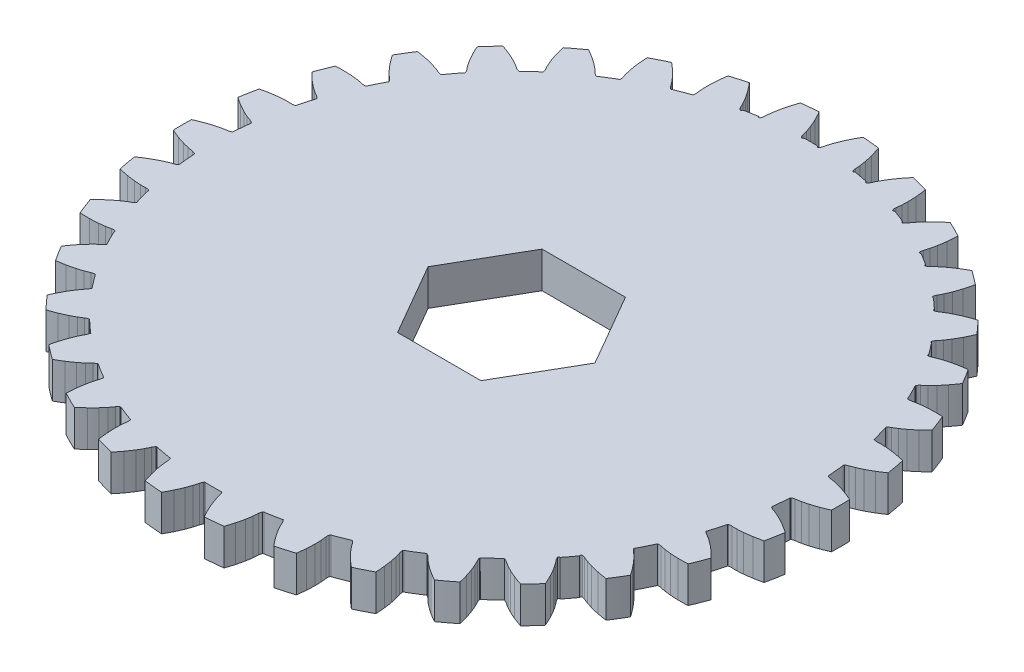
SolidWorks part; units mm, degrees
ref_plane "Front Plane" through (0, 0, 0) normal (0, 0, 1) x (1, 0, 0)
ref_plane "Top Plane" through (0, 0, 0) normal (0, 1, 0) x (1, 0, 0)
ref_plane "Right Plane" through (0, 0, 0) normal (1, 0, 0) x (0, 0, -1)
sketch "Model" plane through (0, 0, 0) normal (0, 1, 0) x (1, 0, 0)
  line L1 (7.3323, 0) -> (3.6662, 6.35)
  line L2 (3.6662, 6.35) -> (-3.6662, 6.35)
  line L3 (-3.6662, 6.35) -> (-7.3323, 0)
  line L4 (-7.3323, 0) -> (-3.6662, -6.35)
  line L5 (-3.6662, -6.35) -> (3.6662, -6.35)
  line L6 (3.6662, -6.35) -> (7.3323, 0)
  circle A0 centre (0, 0) radius 27.7 construction
  arc A1 (26.1185, -2.4202) -> (26.1766, -1.6798) centre (0, 0) ccw
  arc A2 (26.2183, -1.6388) -> (26.1766, -1.6798) centre (26.263, -1.726) ccw
  arc A3 (26.4889, -1.5535) -> (26.2183, -1.6388) centre (26.6041, -2.3907) ccw
  arc A4 (26.4889, -1.5535) -> (26.9416, -1.473) centre (25.6873, 4.2688) ccw
  arc A5 (26.9416, -1.473) -> (27.4742, -1.3382) centre (25.1508, 6.7249) ccw
  arc A6 (27.4742, -1.3382) -> (28.1662, -1.11) centre (24.8202, 7.8723) ccw
  arc A7 (28.1662, -1.11) -> (28.9229, -0.7986) centre (23.9466, 10.2174) ccw
  arc A8 (28.9229, -0.7986) -> (28.9229, 0.7986) centre (0, 0) ccw
  arc A9 (28.9229, 0.7986) -> (28.1662, 1.11) centre (23.9466, -10.2174) ccw
  arc A10 (28.1662, 1.11) -> (27.4742, 1.3382) centre (24.8202, -7.8723) ccw
  arc A11 (27.4742, 1.3382) -> (26.9416, 1.473) centre (25.1508, -6.7249) ccw
  arc A12 (26.9416, 1.473) -> (26.4889, 1.5535) centre (25.6873, -4.2688) ccw
  arc A13 (26.2183, 1.6388) -> (26.4889, 1.5535) centre (26.6041, 2.3907) ccw
  arc A14 (26.1675, 1.6852) -> (26.2183, 1.6388) centre (26.2566, 1.7318) ccw
  arc A15 (26.1675, 1.6852) -> (26.0357, 3.1176) centre (0, 0) ccw
  arc A16 (26.073, 3.2067) -> (26.0357, 3.1176) centre (26.133, 3.1292) ccw
  arc A17 (26.3233, 3.3403) -> (26.073, 3.2067) centre (26.5904, 2.5385) ccw
  arc A18 (26.3233, 3.3403) -> (26.7535, 3.5026) centre (24.4655, 8.9161) ccw
  arc A19 (26.7535, 3.5026) -> (27.2523, 3.7329) centre (23.4869, 11.2318) ccw
  arc A20 (27.2523, 3.7329) -> (27.8906, 4.0844) centre (22.951, 12.2989) ccw
  arc A21 (27.8906, 4.0844) -> (28.5771, 4.5296) centre (21.6614, 14.4436) ccw
  arc A22 (28.5771, 4.5296) -> (28.2837, 6.0995) centre (0, 0) ccw
  arc A23 (28.2837, 6.0995) -> (27.4827, 6.2666) centre (25.4163, -5.6432) ccw
  arc A24 (27.4827, 6.2666) -> (26.7605, 6.3638) centre (25.8441, -3.1775) ccw
  arc A25 (26.7605, 6.3638) -> (26.2122, 6.3984) centre (25.9582, -1.9889) ccw
  arc A26 (26.2122, 6.3984) -> (25.7524, 6.3943) centre (26.0343, 0.5239) ccw
  arc A27 (25.4707, 6.4285) -> (25.7524, 6.3943) centre (25.7119, 7.2385) ccw
  arc A28 (25.4168, 6.447) -> (25.4707, 6.4285) centre (25.4771, 6.5347) ccw
  arc A29 (25.4168, 6.447) -> (25.0195, 7.8485) centre (0, 0) ccw
  arc A30 (25.0398, 7.943) -> (25.0195, 7.8485) centre (25.113, 7.8779) ccw
  arc A31 (25.2613, 8.1203) -> (25.0398, 7.943) centre (25.6712, 7.3813) ccw
  arc A32 (25.2613, 8.1203) -> (25.6544, 8.3589) centre (22.4106, 13.2599) ccw
  arc A33 (25.6544, 8.3589) -> (26.1024, 8.677) centre (21.0231, 15.3563) ccw
  arc A34 (26.1024, 8.677) -> (26.6652, 9.1398) centre (20.3003, 16.3068) ccw
  arc A35 (26.6652, 9.1398) -> (27.2583, 9.7035) centre (18.6386, 18.1779) ccw
  arc A36 (27.2583, 9.7035) -> (26.6813, 11.1928) centre (0, 0) ccw
  arc A37 (26.6813, 11.1928) -> (25.8632, 11.2099) centre (26.0205, -0.8769) ccw
  arc A38 (25.8632, 11.2099) -> (25.1355, 11.1727) centre (25.9879, 1.6254) ccw
  arc A39 (25.1355, 11.1727) -> (24.5902, 11.1059) centre (25.8817, 2.8148) ccw
  arc A40 (24.5902, 11.1059) -> (24.139, 11.0175) centre (25.4948, 5.2988) ccw
  arc A41 (23.8558, 10.9993) -> (24.139, 11.0175) centre (23.944, 11.8398) ccw
  arc A42 (23.8034, 10.9988) -> (23.8558, 10.9993) centre (23.8287, 11.1089) ccw
  arc A43 (23.8034, 10.9988) -> (23.1514, 12.3122) centre (0, 0) ccw
  arc A44 (23.154, 12.4088) -> (23.1514, 12.3122) centre (23.2379, 12.3582) ccw
  arc A45 (23.3391, 12.6238) -> (23.154, 12.4088) centre (23.8778, 11.9727) ccw
  arc A46 (23.3391, 12.6238) -> (23.6816, 12.9306) centre (19.5926, 17.152) ccw
  arc A47 (23.6816, 12.9306) -> (24.0635, 13.3255) centre (17.8434, 18.9578) ccw
  arc A48 (24.0635, 13.3255) -> (24.5317, 13.8838) centre (16.9583, 19.7593) ccw
  arc A49 (24.5317, 13.8838) -> (25.0418, 14.5927) centre (14.981, 21.2932) ccw
  arc A50 (25.0418, 14.5927) -> (24.225, 15.9119) centre (0, 0) ccw
  arc A51 (24.225, 15.9119) -> (23.363, 15.7713) centre (25.7385, 3.9192) ccw
  arc A52 (23.363, 15.7713) -> (22.6546, 15.6011) centre (25.2467, 6.373) ccw
  arc A53 (22.6546, 15.6011) -> (22.1308, 15.4353) centre (24.9238, 7.5226) ccw
  arc A54 (22.1308, 15.4353) -> (21.7035, 15.2654) centre (24.087, 9.8932) ccw
  arc A55 (21.4285, 15.1955) -> (21.7035, 15.2654) centre (21.3607, 16.0379) ccw
  arc A56 (21.4336, 15.196) -> (21.4285, 15.1955) centre (21.4207, 15.2932) ccw
  arc A57 (21.4336, 15.196) -> (20.5895, 16.3215) centre (0, 0) ccw
  arc A58 (20.4796, 16.4521) -> (20.5895, 16.3215) centre (20.5714, 16.4178) ccw
  arc A59 (20.6221, 16.6974) -> (20.4796, 16.4521) centre (21.2713, 16.1563) ccw
  arc A60 (20.6221, 16.6974) -> (20.9024, 17.0619) centre (16.1073, 20.4601) ccw
  arc A61 (20.9024, 17.0619) -> (21.2052, 17.5203) centre (14.0561, 21.9137) ccw
  arc A62 (21.2052, 17.5203) -> (21.5629, 18.1551) centre (13.0388, 22.5389) ccw
  arc A63 (21.5629, 18.1551) -> (21.9401, 18.96) centre (10.8133, 23.6834) ccw
  arc A64 (21.9401, 18.96) -> (20.9035, 20.0971) centre (0, 0) ccw
  arc A65 (20.9035, 20.0971) -> (20.0673, 19.7958) centre (24.5801, 8.582) ccw
  arc A66 (20.0673, 19.7958) -> (19.4021, 19.4982) centre (23.6458, 10.9036) ccw
  arc A67 (19.4021, 19.4982) -> (18.9177, 19.239) centre (23.1172, 11.9742) ccw
  arc A68 (18.9177, 19.239) -> (18.5289, 18.9935) centre (21.859, 14.1507) ccw
  arc A69 (18.2715, 18.8742) -> (18.5289, 18.9935) centre (18.0501, 19.6899) ccw
  arc A70 (18.2887, 18.8807) -> (18.2715, 18.8742) centre (18.2458, 18.9688) ccw
  arc A71 (18.2887, 18.8807) -> (17.2519, 19.8325) centre (0, 0) ccw
  arc A72 (17.1078, 19.935) -> (17.2519, 19.8325) centre (17.2044, 19.9182) ccw
  arc A73 (17.2028, 20.2024) -> (17.1078, 19.935) centre (17.9404, 19.7898) ccw
  arc A74 (17.2028, 20.2024) -> (17.4114, 20.6122) centre (12.0735, 23.0714) ccw
  arc A75 (17.4114, 20.6122) -> (17.6248, 21.1184) centre (9.7902, 24.1234) ccw
  arc A76 (17.6248, 21.1184) -> (17.8597, 21.8082) centre (8.6753, 24.551) ccw
  arc A77 (17.8597, 21.8082) -> (18.0855, 22.6818) centre (6.2774, 25.2671) ccw
  arc A78 (18.0855, 22.6818) -> (16.8666, 23.6023) centre (0, 0) ccw
  arc A79 (16.8666, 23.6023) -> (16.0881, 23.146) centre (22.5847, 12.9524) ccw
  arc A80 (16.0881, 23.146) -> (15.489, 22.7314) centre (21.2397, 15.0628) ccw
  arc A81 (15.489, 22.7314) -> (15.0605, 22.3875) centre (20.5233, 16.0181) ccw
  arc A82 (15.0605, 22.3875) -> (14.7234, 22.0748) centre (18.8866, 17.9264) ccw
  arc A83 (14.4923, 21.9102) -> (14.7234, 22.0748) centre (14.1247, 22.6713) ccw
  arc A84 (14.5162, 21.9266) -> (14.4923, 21.9102) centre (14.4496, 21.9985) ccw
  arc A85 (14.5162, 21.9266) -> (13.3218, 22.6721) centre (0, 0) ccw
  arc A86 (13.1535, 22.7392) -> (13.3218, 22.6721) centre (13.2515, 22.7404) ccw
  arc A87 (13.1977, 23.0194) -> (13.1535, 22.7392) centre (13.9986, 22.7494) ccw
  arc A88 (13.1977, 23.0194) -> (13.3275, 23.4605) centre (7.6285, 24.8971) ccw
  arc A89 (13.3275, 23.4605) -> (13.4442, 23.9974) centre (5.1908, 25.5116) ccw
  arc A90 (13.4442, 23.9974) -> (13.5484, 24.7186) centre (4.0163, 25.7271) ccw
  arc A91 (13.5484, 24.7186) -> (13.6101, 25.6297) centre (1.5277, 25.9904) ccw
  arc A92 (13.6101, 25.6297) -> (12.251, 26.3064) centre (0, 0) ccw
  arc A93 (12.251, 26.3064) -> (11.5611, 25.7081) centre (19.8201, 16.8818) ccw
  arc A94 (11.5611, 25.7081) -> (11.0484, 25.1904) centre (18.1103, 18.7091) ccw
  arc A95 (11.0484, 25.1904) -> (10.6903, 24.7737) centre (17.2305, 19.5165) ccw
  arc A96 (10.6903, 24.7737) -> (10.4165, 24.4043) centre (15.2711, 21.0916) ccw
  arc A97 (10.2195, 24.2001) -> (10.4165, 24.4043) centre (9.7184, 24.8807) ccw
  arc A98 (10.2447, 24.2274) -> (10.2195, 24.2001) centre (10.1614, 24.279) ccw
  arc A99 (10.2447, 24.2274) -> (8.9332, 24.741) centre (0, 0) ccw
  arc A100 (8.7512, 24.7689) -> (8.9332, 24.741) centre (8.8473, 24.7881) ccw
  arc A101 (8.7432, 25.0526) -> (8.7512, 24.7689) centre (9.58, 24.9343) ccw
  arc A102 (8.7432, 25.0526) -> (8.7897, 25.51) centre (2.9238, 25.8749) ccw
  arc A103 (8.7897, 25.51) -> (8.8058, 26.0592) centre (0.4147, 26.031) ccw
  arc A104 (8.8058, 26.0592) -> (8.7757, 26.7872) centre (-0.7794, 26.027) ccw
  arc A105 (8.7757, 26.7872) -> (8.6677, 27.702) centre (-3.2741, 25.8285) ccw
  arc A106 (8.6677, 27.702) -> (7.2138, 28.1157) centre (0, 0) ccw
  arc A107 (7.2138, 28.1157) -> (6.6404, 27.3947) centre (16.3806, 20.2363) ccw
  arc A108 (6.6404, 27.3947) -> (6.2315, 26.7916) centre (14.3641, 21.7183) ccw
  arc A109 (6.2315, 26.7916) -> (5.9562, 26.3162) centre (13.351, 22.3503) ccw
  arc A110 (5.9562, 26.3162) -> (5.7549, 25.9028) centre (11.1355, 23.5385) ccw
  arc A111 (5.5987, 25.6659) -> (5.7549, 25.9028) centre (4.9811, 26.2428) ccw
  arc A112 (5.6203, 25.7026) -> (5.5987, 25.6659) centre (5.5271, 25.7328) ccw
  arc A113 (5.6203, 25.7026) -> (4.2365, 25.9665) centre (0, 0) ccw
  arc A114 (4.0509, 25.9552) -> (4.2365, 25.9665) centre (4.1419, 25.9917) ccw
  arc A115 (3.9909, 26.2325) -> (4.0509, 25.9552) centre (4.8352, 26.2701) ccw
  arc A116 (3.9909, 26.2325) -> (3.9526, 26.6907) centre (-1.8805, 25.9716) ccw
  arc A117 (3.9526, 26.6907) -> (3.8675, 27.2335) centre (-4.3756, 25.664) ccw
  arc A118 (3.8675, 27.2335) -> (3.7041, 27.9436) centre (-5.5486, 25.4406) ccw
  arc A119 (3.7041, 27.9436) -> (3.4283, 28.8275) centre (-7.9643, 24.7872) ccw
  arc A120 (3.4283, 28.8275) -> (1.9271, 28.9666) centre (0, 0) ccw
  arc A121 (1.9271, 28.9666) -> (1.4936, 28.1485) centre (12.3833, 22.9017) ccw
  arc A122 (1.4936, 28.1485) -> (1.2025, 27.4805) centre (10.1288, 23.9879) ccw
  arc A123 (1.2025, 27.4805) -> (1.0191, 26.9626) centre (9.0168, 24.423) ccw
  arc A124 (1.0191, 26.9626) -> (0.8972, 26.5192) centre (6.6207, 25.1839) ccw
  arc A125 (0.7873, 26.2576) -> (0.8972, 26.5192) centre (0.0742, 26.7112) ccw
  arc A126 (0.8021, 26.3003) -> (0.7873, 26.2576) centre (0.7046, 26.3102) ccw
  arc A127 (0.8021, 26.3003) -> (-0.6068, 26.3056) centre (0, 0) ccw
  arc A128 (-0.7873, 26.2576) -> (-0.6068, 26.3056) centre (-0.7046, 26.3102) ccw
  arc A129 (-0.8972, 26.5192) -> (-0.7873, 26.2576) centre (-0.0742, 26.7112) ccw
  arc A130 (-0.8972, 26.5192) -> (-1.0191, 26.9626) centre (-6.6207, 25.1839) ccw
  arc A131 (-1.0191, 26.9626) -> (-1.2025, 27.4805) centre (-9.0168, 24.423) ccw
  arc A132 (-1.2025, 27.4805) -> (-1.4936, 28.1485) centre (-10.1288, 23.9879) ccw
  arc A133 (-1.4936, 28.1485) -> (-1.9277, 28.9676) centre (-12.3833, 22.9017) ccw
  arc A134 (-1.9277, 28.9676) -> (-3.4279, 28.8286) centre (0, 0) ccw
  arc A135 (-3.4279, 28.8286) -> (-3.7041, 27.9436) centre (7.9643, 24.7872) ccw
  arc A136 (-3.7041, 27.9436) -> (-3.8675, 27.2335) centre (5.5486, 25.4406) ccw
  arc A137 (-3.8675, 27.2335) -> (-3.9526, 26.6907) centre (4.3756, 25.664) ccw
  arc A138 (-3.9526, 26.6907) -> (-3.9909, 26.2325) centre (1.8805, 25.9716) ccw
  arc A139 (-4.0509, 25.9552) -> (-3.9909, 26.2325) centre (-4.8352, 26.2701) ccw
  arc A140 (-4.0442, 25.9995) -> (-4.0509, 25.9552) centre (-4.1419, 25.9917) ccw
  arc A141 (-4.0442, 25.9995) -> (-5.43, 25.7458) centre (0, 0) ccw
  arc A142 (-5.5987, 25.6659) -> (-5.43, 25.7458) centre (-5.5271, 25.7328) ccw
  arc A143 (-5.7549, 25.9028) -> (-5.5987, 25.6659) centre (-4.9811, 26.2428) ccw
  arc A144 (-5.7549, 25.9028) -> (-5.9562, 26.3162) centre (-11.1355, 23.5385) ccw
  arc A145 (-5.9562, 26.3162) -> (-6.2315, 26.7916) centre (-13.351, 22.3503) ccw
  arc A146 (-6.2315, 26.7916) -> (-6.6404, 27.3947) centre (-14.3641, 21.7183) ccw
  arc A147 (-6.6404, 27.3947) -> (-7.2161, 28.1184) centre (-16.3806, 20.2363) ccw
  arc A148 (-7.2161, 28.1184) -> (-8.6671, 27.7055) centre (0, 0) ccw
  arc A149 (-8.6671, 27.7055) -> (-8.7757, 26.7872) centre (3.2741, 25.8285) ccw
  arc A150 (-8.7757, 26.7872) -> (-8.8058, 26.0592) centre (0.7794, 26.027) ccw
  arc A151 (-8.8058, 26.0592) -> (-8.7897, 25.51) centre (-0.4147, 26.031) ccw
  arc A152 (-8.7897, 25.51) -> (-8.7432, 25.0526) centre (-2.9238, 25.8749) ccw
  arc A153 (-8.7512, 24.7689) -> (-8.7432, 25.0526) centre (-9.58, 24.9343) ccw
  arc A154 (-8.7401, 24.7222) -> (-8.7512, 24.7689) centre (-8.8779, 24.7141) ccw
  arc A155 (-8.7401, 24.7222) -> (-10.1236, 24.1886) centre (0, 0) ccw
  arc A156 (-10.2195, 24.2001) -> (-10.1236, 24.1886) centre (-10.1614, 24.279) ccw
  arc A157 (-10.4165, 24.4043) -> (-10.2195, 24.2001) centre (-9.7184, 24.8807) ccw
  arc A158 (-10.4165, 24.4043) -> (-10.6903, 24.7737) centre (-15.2711, 21.0916) ccw
  arc A159 (-10.6903, 24.7737) -> (-11.0484, 25.1904) centre (-17.2305, 19.5165) ccw
  arc A160 (-11.0484, 25.1904) -> (-11.5611, 25.7081) centre (-18.1103, 18.7091) ccw
  arc A161 (-11.5611, 25.7081) -> (-12.1772, 26.2467) centre (-19.8201, 16.8818) ccw
  arc A162 (-12.1772, 26.2467) -> (-13.6069, 25.5347) centre (0, 0) ccw
  arc A163 (-13.6069, 25.5347) -> (-13.5484, 24.7186) centre (-1.5277, 25.9904) ccw
  arc A164 (-13.5484, 24.7186) -> (-13.4442, 23.9974) centre (-4.0163, 25.7271) ccw
  arc A165 (-13.4442, 23.9974) -> (-13.3275, 23.4605) centre (-5.1908, 25.5116) ccw
  arc A166 (-13.3275, 23.4605) -> (-13.1977, 23.0194) centre (-7.6285, 24.8971) ccw
  arc A167 (-13.1535, 22.7392) -> (-13.1977, 23.0194) centre (-13.9986, 22.7494) ccw
  arc A168 (-13.1353, 22.6945) -> (-13.1535, 22.7392) centre (-13.2668, 22.6671) ccw
  arc A169 (-13.1353, 22.6945) -> (-14.3959, 21.9166) centre (0, 0) ccw
  arc A170 (-14.4923, 21.9102) -> (-14.3959, 21.9166) centre (-14.4496, 21.9985) ccw
  arc A171 (-14.7234, 22.0748) -> (-14.4923, 21.9102) centre (-14.1247, 22.6713) ccw
  arc A172 (-14.7234, 22.0748) -> (-15.0605, 22.3875) centre (-18.8866, 17.9264) ccw
  arc A173 (-15.0605, 22.3875) -> (-15.489, 22.7314) centre (-20.5233, 16.0181) ccw
  arc A174 (-15.489, 22.7314) -> (-16.0881, 23.146) centre (-21.2397, 15.0628) ccw
  arc A175 (-16.0881, 23.146) -> (-16.7926, 23.5622) centre (-22.5847, 12.9524) ccw
  arc A176 (-16.7926, 23.5622) -> (-18.0672, 22.5997) centre (0, 0) ccw
  arc A177 (-18.0672, 22.5997) -> (-17.8597, 21.8082) centre (-6.2774, 25.2671) ccw
  arc A178 (-17.8597, 21.8082) -> (-17.6248, 21.1184) centre (-8.6753, 24.551) ccw
  arc A179 (-17.6248, 21.1184) -> (-17.4114, 20.6122) centre (-9.7902, 24.1234) ccw
  arc A180 (-17.4114, 20.6122) -> (-17.2028, 20.2024) centre (-12.0735, 23.0714) ccw
  arc A181 (-17.1078, 19.935) -> (-17.2028, 20.2024) centre (-17.9404, 19.7898) ccw
  arc A182 (-17.0837, 19.8928) -> (-17.1078, 19.935) centre (-17.2059, 19.851) ccw
  arc A183 (-17.0837, 19.8928) -> (-18.1779, 18.8982) centre (0, 0) ccw
  arc A184 (-18.2715, 18.8742) -> (-18.1779, 18.8982) centre (-18.2458, 18.9688) ccw
  arc A185 (-18.5289, 18.9935) -> (-18.2715, 18.8742) centre (-18.0501, 19.6899) ccw
  arc A186 (-18.5289, 18.9935) -> (-18.9177, 19.239) centre (-21.859, 14.1507) ccw
  arc A187 (-18.9177, 19.239) -> (-19.4021, 19.4982) centre (-23.1172, 11.9742) ccw
  arc A188 (-19.4021, 19.4982) -> (-20.0673, 19.7958) centre (-23.6458, 10.9036) ccw
  arc A189 (-20.0673, 19.7958) -> (-20.8363, 20.0754) centre (-24.5801, 8.582) ccw
  arc A190 (-20.8363, 20.0754) -> (-21.9123, 18.8951) centre (0, 0) ccw
  arc A191 (-21.9123, 18.8951) -> (-21.5629, 18.1551) centre (-10.8133, 23.6834) ccw
  arc A192 (-21.5629, 18.1551) -> (-21.2052, 17.5203) centre (-13.0388, 22.5389) ccw
  arc A193 (-21.2052, 17.5203) -> (-20.9024, 17.0619) centre (-14.0561, 21.9137) ccw
  arc A194 (-20.9024, 17.0619) -> (-20.6221, 16.6974) centre (-16.1073, 20.4601) ccw
  arc A195 (-20.4796, 16.4521) -> (-20.6221, 16.6974) centre (-21.2713, 16.1563) ccw
  arc A196 (-20.4506, 16.4119) -> (-20.4796, 16.4521) centre (-20.5624, 16.3616) ccw
  arc A197 (-20.4506, 16.4119) -> (-21.3409, 15.2362) centre (0, 0) ccw
  arc A198 (-21.4285, 15.1955) -> (-21.3409, 15.2362) centre (-21.4207, 15.2932) ccw
  arc A199 (-21.7035, 15.2654) -> (-21.4285, 15.1955) centre (-21.3607, 16.0379) ccw
  arc A200 (-21.7035, 15.2654) -> (-22.1308, 15.4353) centre (-24.087, 9.8932) ccw
  arc A201 (-22.1308, 15.4353) -> (-22.6546, 15.6011) centre (-24.9238, 7.5226) ccw
  arc A202 (-22.6546, 15.6011) -> (-23.363, 15.7713) centre (-25.2467, 6.373) ccw
  arc A203 (-23.363, 15.7713) -> (-24.1703, 15.9049) centre (-25.7385, 3.9192) ccw
  arc A204 (-24.1703, 15.9049) -> (-25.0111, 14.547) centre (0, 0) ccw
  arc A205 (-25.0111, 14.547) -> (-24.5317, 13.8838) centre (-14.981, 21.2932) ccw
  arc A206 (-24.5317, 13.8838) -> (-24.0635, 13.3255) centre (-16.9583, 19.7593) ccw
  arc A207 (-24.0635, 13.3255) -> (-23.6816, 12.9306) centre (-17.8434, 18.9578) ccw
  arc A208 (-23.6816, 12.9306) -> (-23.3391, 12.6238) centre (-19.5926, 17.152) ccw
  arc A209 (-23.154, 12.4088) -> (-23.3391, 12.6238) centre (-23.8778, 11.9727) ccw
  arc A210 (-23.1209, 12.3694) -> (-23.154, 12.4088) centre (-23.2234, 12.3168) ccw
  arc A211 (-23.1209, 12.3694) -> (-23.7772, 11.0554) centre (0, 0) ccw
  arc A212 (-23.8558, 10.9993) -> (-23.7772, 11.0554) centre (-23.866, 11.0967) ccw
  arc A213 (-24.139, 11.0175) -> (-23.8558, 10.9993) centre (-23.944, 11.8398) ccw
  arc A214 (-24.139, 11.0175) -> (-24.5902, 11.1059) centre (-25.4948, 5.2988) ccw
  arc A215 (-24.5902, 11.1059) -> (-25.1355, 11.1727) centre (-25.8817, 2.8148) ccw
  arc A216 (-25.1355, 11.1727) -> (-25.8632, 11.2099) centre (-25.9879, 1.6254) ccw
  arc A217 (-25.8632, 11.2099) -> (-26.6813, 11.1928) centre (-26.0205, -0.8769) ccw
  arc A218 (-26.6813, 11.1928) -> (-27.2583, 9.7035) centre (0, 0) ccw
  arc A219 (-27.2583, 9.7035) -> (-26.6652, 9.1398) centre (-18.6386, 18.1779) ccw
  arc A220 (-26.6652, 9.1398) -> (-26.1024, 8.677) centre (-20.3003, 16.3068) ccw
  arc A221 (-26.1024, 8.677) -> (-25.6544, 8.3589) centre (-21.0231, 15.3563) ccw
  arc A222 (-25.6544, 8.3589) -> (-25.2613, 8.1203) centre (-22.4106, 13.2599) ccw
  arc A223 (-25.0398, 7.943) -> (-25.2613, 8.1203) centre (-25.6712, 7.3813) ccw
  arc A224 (-25.0029, 7.9012) -> (-25.0398, 7.943) centre (-25.0995, 7.8532) ccw
  arc A225 (-25.0029, 7.9012) -> (-25.4038, 6.4981) centre (0, 0) ccw
  arc A226 (-25.4707, 6.4285) -> (-25.4038, 6.4981) centre (-25.4987, 6.5224) ccw
  arc A227 (-25.7524, 6.3943) -> (-25.4707, 6.4285) centre (-25.7119, 7.2385) ccw
  arc A228 (-25.7524, 6.3943) -> (-26.2122, 6.3984) centre (-26.0343, 0.5239) ccw
  arc A229 (-26.2122, 6.3984) -> (-26.7605, 6.3638) centre (-25.9582, -1.9889) ccw
  arc A230 (-26.7605, 6.3638) -> (-27.4827, 6.2666) centre (-25.8441, -3.1775) ccw
  arc A231 (-27.4827, 6.2666) -> (-28.2837, 6.0995) centre (-25.4163, -5.6432) ccw
  arc A232 (-28.2837, 6.0995) -> (-28.5771, 4.5296) centre (0, 0) ccw
  arc A233 (-28.5771, 4.5296) -> (-27.8906, 4.0844) centre (-21.6614, 14.4436) ccw
  arc A234 (-27.8906, 4.0844) -> (-27.2523, 3.7329) centre (-22.951, 12.2989) ccw
  arc A235 (-27.2523, 3.7329) -> (-26.7535, 3.5026) centre (-23.4869, 11.2318) ccw
  arc A236 (-26.7535, 3.5026) -> (-26.3233, 3.3403) centre (-24.4655, 8.9161) ccw
  arc A237 (-26.073, 3.2067) -> (-26.3233, 3.3403) centre (-26.5904, 2.5385) ccw
  arc A238 (-26.0313, 3.1538) -> (-26.073, 3.2067) centre (-26.1269, 3.1214) ccw
  arc A239 (-26.0313, 3.1538) -> (-26.1652, 1.7195) centre (0, 0) ccw
  arc A240 (-26.2183, 1.6388) -> (-26.1652, 1.7195) centre (-26.263, 1.726) ccw
  arc A241 (-26.4889, 1.5535) -> (-26.2183, 1.6388) centre (-26.6041, 2.3907) ccw
  arc A242 (-26.4889, 1.5535) -> (-26.9416, 1.473) centre (-25.6873, -4.2688) ccw
  arc A243 (-26.9416, 1.473) -> (-27.4742, 1.3382) centre (-25.1508, -6.7249) ccw
  arc A244 (-27.4742, 1.3382) -> (-28.1662, 1.11) centre (-24.8202, -7.8723) ccw
  arc A245 (-28.1662, 1.11) -> (-28.9229, 0.7986) centre (-23.9466, -10.2174) ccw
  arc A246 (-28.9229, 0.7986) -> (-28.9229, -0.7986) centre (0, 0) ccw
  arc A247 (-28.9229, -0.7986) -> (-28.1662, -1.11) centre (-23.9466, 10.2174) ccw
  arc A248 (-28.1662, -1.11) -> (-27.4742, -1.3382) centre (-24.8202, 7.8723) ccw
  arc A249 (-27.4742, -1.3382) -> (-26.9416, -1.473) centre (-25.1508, 6.7249) ccw
  arc A250 (-26.9416, -1.473) -> (-26.4889, -1.5535) centre (-25.6873, 4.2688) ccw
  arc A251 (-26.2183, -1.6388) -> (-26.4889, -1.5535) centre (-26.6041, -2.3907) ccw
  arc A252 (-26.1719, -1.762) -> (-26.2183, -1.6388) centre (-26.263, -1.726) ccw
  arc A253 (-26.1719, -1.762) -> (-26.0401, -3.1604) centre (0, 0) ccw
  arc A254 (-26.073, -3.2067) -> (-26.0401, -3.1604) centre (-26.133, -3.1292) ccw
  arc A255 (-26.3233, -3.3403) -> (-26.073, -3.2067) centre (-26.5904, -2.5385) ccw
  arc A256 (-26.3233, -3.3403) -> (-26.7535, -3.5026) centre (-24.4655, -8.9161) ccw
  arc A257 (-26.7535, -3.5026) -> (-27.2523, -3.7329) centre (-23.4869, -11.2318) ccw
  arc A258 (-27.2523, -3.7329) -> (-27.8906, -4.0844) centre (-22.951, -12.2989) ccw
  arc A259 (-27.8906, -4.0844) -> (-28.595, -4.5421) centre (-21.6614, -14.4436) ccw
  arc A260 (-28.595, -4.5421) -> (-28.3049, -6.0944) centre (0, 0) ccw
  arc A261 (-28.3049, -6.0944) -> (-27.4827, -6.2666) centre (-25.4163, 5.6432) ccw
  arc A262 (-27.4827, -6.2666) -> (-26.7605, -6.3638) centre (-25.8441, 3.1775) ccw
  arc A263 (-26.7605, -6.3638) -> (-26.2122, -6.3984) centre (-25.9582, 1.9889) ccw
  arc A264 (-26.2122, -6.3984) -> (-25.7524, -6.3943) centre (-26.0343, -0.5239) ccw
  arc A265 (-25.4707, -6.4285) -> (-25.7524, -6.3943) centre (-25.7119, -7.2385) ccw
  arc A266 (-25.4134, -6.5706) -> (-25.4707, -6.4285) centre (-25.4987, -6.5224) ccw
  arc A267 (-25.4134, -6.5706) -> (-25.0253, -7.9214) centre (0, 0) ccw
  arc A268 (-25.0398, -7.943) -> (-25.0253, -7.9214) centre (-25.113, -7.8779) ccw
  arc A269 (-25.2613, -8.1203) -> (-25.0398, -7.943) centre (-25.6712, -7.3813) ccw
  arc A270 (-25.2613, -8.1203) -> (-25.6544, -8.3589) centre (-22.4106, -13.2599) ccw
  arc A271 (-25.6544, -8.3589) -> (-26.1024, -8.677) centre (-21.0231, -15.3563) ccw
  arc A272 (-26.1024, -8.677) -> (-26.6652, -9.1398) centre (-20.3003, -16.3068) ccw
  arc A273 (-26.6652, -9.1398) -> (-27.288, -9.7339) centre (-18.6386, -18.1779) ccw
  arc A274 (-27.288, -9.7339) -> (-26.7237, -11.1904) centre (0, 0) ccw
  arc A275 (-26.7237, -11.1904) -> (-25.8632, -11.2099) centre (-26.0205, 0.8769) ccw
  arc A276 (-25.8632, -11.2099) -> (-25.1355, -11.1727) centre (-25.9879, -1.6254) ccw
  arc A277 (-25.1355, -11.1727) -> (-24.5902, -11.1059) centre (-25.8817, -2.8148) ccw
  arc A278 (-24.5902, -11.1059) -> (-24.139, -11.0175) centre (-25.4948, -5.2988) ccw
  arc A279 (-23.8558, -10.9993) -> (-24.139, -11.0175) centre (-23.944, -11.8398) ccw
  arc A280 (-23.7824, -11.1478) -> (-23.8558, -10.9993) centre (-23.866, -11.0967) ccw
  arc A281 (-23.7824, -11.1478) -> (-23.1517, -12.4048) centre (0, 0) ccw
  arc A282 (-23.154, -12.4088) -> (-23.1517, -12.4048) centre (-23.2379, -12.3582) ccw
  arc A283 (-23.3391, -12.6238) -> (-23.154, -12.4088) centre (-23.8778, -11.9727) ccw
  arc A284 (-23.3391, -12.6238) -> (-23.6816, -12.9306) centre (-19.5926, -17.152) ccw
  arc A285 (-23.6816, -12.9306) -> (-24.0635, -13.3255) centre (-17.8434, -18.9578) ccw
  arc A286 (-24.0635, -13.3255) -> (-24.5317, -13.8838) centre (-16.9583, -19.7593) ccw
  arc A287 (-24.5317, -13.8838) -> (-25.0111, -14.547) centre (-14.981, -21.2932) ccw
  arc A288 (-25.0111, -14.547) -> (-24.1703, -15.9049) centre (0, 0) ccw
  arc A289 (-24.1703, -15.9049) -> (-23.363, -15.7713) centre (-25.7385, -3.9192) ccw
  arc A290 (-23.363, -15.7713) -> (-22.6546, -15.6011) centre (-25.2467, -6.373) ccw
  arc A291 (-22.6546, -15.6011) -> (-22.1308, -15.4353) centre (-24.9238, -7.5226) ccw
  arc A292 (-22.1308, -15.4353) -> (-21.7035, -15.2654) centre (-24.087, -9.8932) ccw
  arc A293 (-21.4285, -15.1955) -> (-21.7035, -15.2654) centre (-21.3607, -16.0379) ccw
  arc A294 (-21.3409, -15.2362) -> (-21.4285, -15.1955) centre (-21.4207, -15.2932) ccw
  arc A295 (-21.3409, -15.2362) -> (-20.4506, -16.4119) centre (0, 0) ccw
  arc A296 (-20.4796, -16.4521) -> (-20.4506, -16.4119) centre (-20.5624, -16.3616) ccw
  arc A297 (-20.6221, -16.6974) -> (-20.4796, -16.4521) centre (-21.2713, -16.1563) ccw
  arc A298 (-20.6221, -16.6974) -> (-20.9024, -17.0619) centre (-16.1073, -20.4601) ccw
  arc A299 (-20.9024, -17.0619) -> (-21.2052, -17.5203) centre (-14.0561, -21.9137) ccw
  arc A300 (-21.2052, -17.5203) -> (-21.5629, -18.1551) centre (-13.0388, -22.5389) ccw
  arc A301 (-21.5629, -18.1551) -> (-21.9123, -18.8951) centre (-10.8133, -23.6834) ccw
  arc A302 (-21.9123, -18.8951) -> (-20.8363, -20.0754) centre (0, 0) ccw
  arc A303 (-20.8363, -20.0754) -> (-20.0673, -19.7958) centre (-24.5801, -8.582) ccw
  arc A304 (-20.0673, -19.7958) -> (-19.4021, -19.4982) centre (-23.6458, -10.9036) ccw
  arc A305 (-19.4021, -19.4982) -> (-18.9177, -19.239) centre (-23.1172, -11.9742) ccw
  arc A306 (-18.9177, -19.239) -> (-18.5289, -18.9935) centre (-21.859, -14.1507) ccw
  arc A307 (-18.2715, -18.8742) -> (-18.5289, -18.9935) centre (-18.0501, -19.6899) ccw
  arc A308 (-18.1779, -18.8982) -> (-18.2715, -18.8742) centre (-18.2458, -18.9688) ccw
  arc A309 (-18.1779, -18.8982) -> (-17.0837, -19.8928) centre (0, 0) ccw
  arc A310 (-17.1078, -19.935) -> (-17.0837, -19.8928) centre (-17.2059, -19.851) ccw
  arc A311 (-17.2028, -20.2024) -> (-17.1078, -19.935) centre (-17.9404, -19.7898) ccw
  arc A312 (-17.2028, -20.2024) -> (-17.4114, -20.6122) centre (-12.0735, -23.0714) ccw
  arc A313 (-17.4114, -20.6122) -> (-17.6248, -21.1184) centre (-9.7902, -24.1234) ccw
  arc A314 (-17.6248, -21.1184) -> (-17.8597, -21.8082) centre (-8.6753, -24.551) ccw
  arc A315 (-17.8597, -21.8082) -> (-18.0672, -22.5997) centre (-6.2774, -25.2671) ccw
  arc A316 (-18.0672, -22.5997) -> (-16.7926, -23.5622) centre (0, 0) ccw
  arc A317 (-16.7926, -23.5622) -> (-16.0881, -23.146) centre (-22.5847, -12.9524) ccw
  arc A318 (-16.0881, -23.146) -> (-15.489, -22.7314) centre (-21.2397, -15.0628) ccw
  arc A319 (-15.489, -22.7314) -> (-15.0605, -22.3875) centre (-20.5233, -16.0181) ccw
  arc A320 (-15.0605, -22.3875) -> (-14.7234, -22.0748) centre (-18.8866, -17.9264) ccw
  arc A321 (-14.4923, -21.9102) -> (-14.7234, -22.0748) centre (-14.1247, -22.6713) ccw
  arc A322 (-14.3959, -21.9166) -> (-14.4923, -21.9102) centre (-14.4496, -21.9985) ccw
  arc A323 (-14.3959, -21.9166) -> (-13.1353, -22.6945) centre (0, 0) ccw
  arc A324 (-13.1535, -22.7392) -> (-13.1353, -22.6945) centre (-13.2668, -22.6671) ccw
  arc A325 (-13.1977, -23.0194) -> (-13.1535, -22.7392) centre (-13.9986, -22.7494) ccw
  arc A326 (-13.1977, -23.0194) -> (-13.3275, -23.4605) centre (-7.6285, -24.8971) ccw
  arc A327 (-13.3275, -23.4605) -> (-13.4442, -23.9974) centre (-5.1908, -25.5116) ccw
  arc A328 (-13.4442, -23.9974) -> (-13.5484, -24.7186) centre (-4.0163, -25.7271) ccw
  arc A329 (-13.5484, -24.7186) -> (-13.6069, -25.5347) centre (-1.5277, -25.9904) ccw
  arc A330 (-13.6069, -25.5347) -> (-12.1772, -26.2467) centre (0, 0) ccw
  arc A331 (-12.1772, -26.2467) -> (-11.5611, -25.7081) centre (-19.8201, -16.8818) ccw
  arc A332 (-11.5611, -25.7081) -> (-11.0484, -25.1904) centre (-18.1103, -18.7091) ccw
  arc A333 (-11.0484, -25.1904) -> (-10.6903, -24.7737) centre (-17.2305, -19.5165) ccw
  arc A334 (-10.6903, -24.7737) -> (-10.4165, -24.4043) centre (-15.2711, -21.0916) ccw
  arc A335 (-10.2195, -24.2001) -> (-10.4165, -24.4043) centre (-9.7184, -24.8807) ccw
  arc A336 (-10.1236, -24.1886) -> (-10.2195, -24.2001) centre (-10.1614, -24.279) ccw
  arc A337 (-10.1236, -24.1886) -> (-8.7401, -24.7222) centre (0, 0) ccw
  arc A338 (-8.7512, -24.7689) -> (-8.7401, -24.7222) centre (-8.8779, -24.7141) ccw
  arc A339 (-8.7432, -25.0526) -> (-8.7512, -24.7689) centre (-9.58, -24.9343) ccw
  arc A340 (-8.7432, -25.0526) -> (-8.7897, -25.51) centre (-2.9238, -25.8749) ccw
  arc A341 (-8.7897, -25.51) -> (-8.8058, -26.0592) centre (-0.4147, -26.031) ccw
  arc A342 (-8.8058, -26.0592) -> (-8.7757, -26.7872) centre (0.7794, -26.027) ccw
  arc A343 (-8.7757, -26.7872) -> (-8.6832, -27.6002) centre (3.2741, -25.8285) ccw
  arc A344 (-8.6832, -27.6002) -> (-7.147, -28.0373) centre (0, 0) ccw
  arc A345 (-7.147, -28.0373) -> (-6.6404, -27.3947) centre (-16.3806, -20.2363) ccw
  arc A346 (-6.6404, -27.3947) -> (-6.2315, -26.7916) centre (-14.3641, -21.7183) ccw
  arc A347 (-6.2315, -26.7916) -> (-5.9562, -26.3162) centre (-13.351, -22.3503) ccw
  arc A348 (-5.9562, -26.3162) -> (-5.7549, -25.9028) centre (-11.1355, -23.5385) ccw
  arc A349 (-5.5987, -25.6659) -> (-5.7549, -25.9028) centre (-4.9811, -26.2428) ccw
  arc A350 (-5.5066, -25.637) -> (-5.5987, -25.6659) centre (-5.5271, -25.7328) ccw
  arc A351 (-5.5066, -25.637) -> (-4.0478, -25.9074) centre (0, 0) ccw
  arc A352 (-4.0509, -25.9552) -> (-4.0478, -25.9074) centre (-4.187, -25.9223) ccw
  arc A353 (-3.9909, -26.2325) -> (-4.0509, -25.9552) centre (-4.8352, -26.2701) ccw
  arc A354 (-3.9909, -26.2325) -> (-3.9526, -26.6907) centre (1.8805, -25.9716) ccw
  arc A355 (-3.9526, -26.6907) -> (-3.8675, -27.2335) centre (4.3756, -25.664) ccw
  arc A356 (-3.8675, -27.2335) -> (-3.7041, -27.9436) centre (5.5486, -25.4406) ccw
  arc A357 (-3.7041, -27.9436) -> (-3.4638, -28.7258) centre (7.9643, -24.7872) ccw
  arc A358 (-3.4638, -28.7258) -> (-1.8735, -28.8732) centre (0, 0) ccw
  arc A359 (-1.8735, -28.8732) -> (-1.4936, -28.1485) centre (-12.3833, -22.9017) ccw
  arc A360 (-1.4936, -28.1485) -> (-1.2025, -27.4805) centre (-10.1288, -23.9879) ccw
  arc A361 (-1.2025, -27.4805) -> (-1.0191, -26.9626) centre (-9.0168, -24.423) ccw
  arc A362 (-1.0191, -26.9626) -> (-0.8972, -26.5192) centre (-6.6207, -25.1839) ccw
  arc A363 (-0.7873, -26.2576) -> (-0.8972, -26.5192) centre (-0.0742, -26.7112) ccw
  arc A364 (-0.702, -26.2123) -> (-0.7873, -26.2576) centre (-0.7046, -26.3102) ccw
  arc A365 (-0.702, -26.2123) -> (0.7817, -26.21) centre (0, 0) ccw
  arc A366 (0.7873, -26.2576) -> (0.7817, -26.21) centre (0.6473, -26.2501) ccw
  arc A367 (0.8972, -26.5192) -> (0.7873, -26.2576) centre (0.0742, -26.7112) ccw
  arc A368 (0.8972, -26.5192) -> (1.0191, -26.9626) centre (6.6207, -25.1839) ccw
  arc A369 (1.0191, -26.9626) -> (1.2025, -27.4805) centre (9.0168, -24.423) ccw
  arc A370 (1.2025, -27.4805) -> (1.4936, -28.1485) centre (10.1288, -23.9879) ccw
  arc A371 (1.4936, -28.1485) -> (1.8735, -28.8732) centre (12.3833, -22.9017) ccw
  arc A372 (1.8735, -28.8732) -> (3.4638, -28.7258) centre (0, 0) ccw
  arc A373 (3.4638, -28.7258) -> (3.7041, -27.9436) centre (-7.9643, -24.7872) ccw
  arc A374 (3.7041, -27.9436) -> (3.8675, -27.2335) centre (-5.5486, -25.4406) ccw
  arc A375 (3.8675, -27.2335) -> (3.9526, -26.6907) centre (-4.3756, -25.664) ccw
  arc A376 (3.9526, -26.6907) -> (3.9909, -26.2325) centre (-1.8805, -25.9716) ccw
  arc A377 (4.0509, -25.9552) -> (3.9909, -26.2325) centre (4.8352, -26.2701) ccw
  arc A378 (4.1264, -25.895) -> (4.0509, -25.9552) centre (4.1419, -25.9917) ccw
  arc A379 (4.1264, -25.895) -> (5.5839, -25.6203) centre (0, 0) ccw
  arc A380 (5.5987, -25.6659) -> (5.5839, -25.6203) centre (5.4613, -25.6853) ccw
  arc A381 (5.7549, -25.9028) -> (5.5987, -25.6659) centre (4.9811, -26.2428) ccw
  arc A382 (5.7549, -25.9028) -> (5.9562, -26.3162) centre (11.1355, -23.5385) ccw
  arc A383 (5.9562, -26.3162) -> (6.2315, -26.7916) centre (13.351, -22.3503) ccw
  arc A384 (6.2315, -26.7916) -> (6.6404, -27.3947) centre (14.3641, -21.7183) ccw
  arc A385 (6.6404, -27.3947) -> (7.147, -28.0373) centre (16.3806, -20.2363) ccw
  arc A386 (7.147, -28.0373) -> (8.6832, -27.6002) centre (0, 0) ccw
  arc A387 (8.6832, -27.6002) -> (8.7757, -26.7872) centre (-3.2741, -25.8285) ccw
  arc A388 (8.7757, -26.7872) -> (8.8058, -26.0592) centre (-0.7794, -26.027) ccw
  arc A389 (8.8058, -26.0592) -> (8.7897, -25.51) centre (0.4147, -26.031) ccw
  arc A390 (8.7897, -25.51) -> (8.7432, -25.0526) centre (2.9238, -25.8749) ccw
  arc A391 (8.7512, -24.7689) -> (8.7432, -25.0526) centre (9.58, -24.9343) ccw
  arc A392 (8.8144, -24.6958) -> (8.7512, -24.7689) centre (8.8473, -24.7881) ccw
  arc A393 (8.8144, -24.6958) -> (10.1954, -24.1585) centre (0, 0) ccw
  arc A394 (10.2195, -24.2001) -> (10.1954, -24.1585) centre (10.0918, -24.2462) ccw
  arc A395 (10.4165, -24.4043) -> (10.2195, -24.2001) centre (9.7184, -24.8807) ccw
  arc A396 (10.4165, -24.4043) -> (10.6903, -24.7737) centre (15.2711, -21.0916) ccw
  arc A397 (10.6903, -24.7737) -> (11.0484, -25.1904) centre (17.2305, -19.5165) ccw
  arc A398 (11.0484, -25.1904) -> (11.5611, -25.7081) centre (18.1103, -18.7091) ccw
  arc A399 (11.5611, -25.7081) -> (12.1772, -26.2467) centre (19.8201, -16.8818) ccw
  arc A400 (12.1772, -26.2467) -> (13.6069, -25.5347) centre (0, 0) ccw
  arc A401 (13.6069, -25.5347) -> (13.5484, -24.7186) centre (1.5277, -25.9904) ccw
  arc A402 (13.5484, -24.7186) -> (13.4442, -23.9974) centre (4.0163, -25.7271) ccw
  arc A403 (13.4442, -23.9974) -> (13.3275, -23.4605) centre (5.1908, -25.5116) ccw
  arc A404 (13.3275, -23.4605) -> (13.1977, -23.0194) centre (7.6285, -24.8971) ccw
  arc A405 (13.1535, -22.7392) -> (13.1977, -23.0194) centre (13.9986, -22.7494) ccw
  arc A406 (13.2021, -22.6557) -> (13.1535, -22.7392) centre (13.2515, -22.7404) ccw
  arc A407 (13.2021, -22.6557) -> (14.4592, -21.8748) centre (0, 0) ccw
  arc A408 (14.4923, -21.9102) -> (14.4592, -21.8748) centre (14.3814, -21.9806) ccw
  arc A409 (14.7234, -22.0748) -> (14.4923, -21.9102) centre (14.1247, -22.6713) ccw
  arc A410 (14.7234, -22.0748) -> (15.0605, -22.3875) centre (18.8866, -17.9264) ccw
  arc A411 (15.0605, -22.3875) -> (15.489, -22.7314) centre (20.5233, -16.0181) ccw
  arc A412 (15.489, -22.7314) -> (16.0881, -23.146) centre (21.2397, -15.0628) ccw
  arc A413 (16.0881, -23.146) -> (16.7926, -23.5622) centre (22.5847, -12.9524) ccw
  arc A414 (16.7926, -23.5622) -> (18.0672, -22.5997) centre (0, 0) ccw
  arc A415 (18.0672, -22.5997) -> (17.8597, -21.8082) centre (6.2774, -25.2671) ccw
  arc A416 (17.8597, -21.8082) -> (17.6248, -21.1184) centre (8.6753, -24.551) ccw
  arc A417 (17.6248, -21.1184) -> (17.4114, -20.6122) centre (9.7902, -24.1234) ccw
  arc A418 (17.4114, -20.6122) -> (17.2028, -20.2024) centre (12.0735, -23.0714) ccw
  arc A419 (17.1078, -19.935) -> (17.2028, -20.2024) centre (17.9404, -19.7898) ccw
  arc A420 (17.1403, -19.8441) -> (17.1078, -19.935) centre (17.2044, -19.9182) ccw
  arc A421 (17.1403, -19.8441) -> (18.2303, -18.8476) centre (0, 0) ccw
  arc A422 (18.2715, -18.8742) -> (18.2303, -18.8476) centre (18.1838, -18.9645) ccw
  arc A423 (18.5289, -18.9935) -> (18.2715, -18.8742) centre (18.0501, -19.6899) ccw
  arc A424 (18.5289, -18.9935) -> (18.9177, -19.239) centre (21.859, -14.1507) ccw
  arc A425 (18.9177, -19.239) -> (19.4021, -19.4982) centre (23.1172, -11.9742) ccw
  arc A426 (19.4021, -19.4982) -> (20.0673, -19.7958) centre (23.6458, -10.9036) ccw
  arc A427 (20.0673, -19.7958) -> (20.9035, -20.0971) centre (24.5801, -8.582) ccw
  arc A428 (20.9035, -20.0971) -> (21.9401, -18.96) centre (0, 0) ccw
  arc A429 (21.9401, -18.96) -> (21.5629, -18.1551) centre (10.8133, -23.6834) ccw
  arc A430 (21.5629, -18.1551) -> (21.2052, -17.5203) centre (13.0388, -22.5389) ccw
  arc A431 (21.2052, -17.5203) -> (20.9024, -17.0619) centre (14.0561, -21.9137) ccw
  arc A432 (20.9024, -17.0619) -> (20.6221, -16.6974) centre (16.1073, -20.4601) ccw
  arc A433 (20.4796, -16.4521) -> (20.6221, -16.6974) centre (21.2713, -16.1563) ccw
  arc A434 (20.485, -16.464) -> (20.4796, -16.4521) centre (20.5714, -16.4178) ccw
  arc A435 (20.485, -16.464) -> (21.4415, -15.1974) centre (0, 0) ccw
  arc A436 (21.4285, -15.1955) -> (21.4415, -15.1974) centre (21.4207, -15.2932) ccw
  arc A437 (21.7035, -15.2654) -> (21.4285, -15.1955) centre (21.3607, -16.0379) ccw
  arc A438 (21.7035, -15.2654) -> (22.1308, -15.4353) centre (24.087, -9.8932) ccw
  arc A439 (22.1308, -15.4353) -> (22.6546, -15.6011) centre (24.9238, -7.5226) ccw
  arc A440 (22.6546, -15.6011) -> (23.363, -15.7713) centre (25.2467, -6.373) ccw
  arc A441 (23.363, -15.7713) -> (24.225, -15.9119) centre (25.7385, -3.9192) ccw
  arc A442 (24.225, -15.9119) -> (25.0418, -14.5927) centre (0, 0) ccw
  arc A443 (25.0418, -14.5927) -> (24.5317, -13.8838) centre (14.981, -21.2932) ccw
  arc A444 (24.5317, -13.8838) -> (24.0635, -13.3255) centre (16.9583, -19.7593) ccw
  arc A445 (24.0635, -13.3255) -> (23.6816, -12.9306) centre (17.8434, -18.9578) ccw
  arc A446 (23.6816, -12.9306) -> (23.3391, -12.6238) centre (19.5926, -17.152) ccw
  arc A447 (23.154, -12.4088) -> (23.3391, -12.6238) centre (23.8778, -11.9727) ccw
  arc A448 (23.1515, -12.4044) -> (23.154, -12.4088) centre (23.2379, -12.3582) ccw
  arc A449 (23.1515, -12.4044) -> (23.8508, -10.9999) centre (0, 0) ccw
  arc A450 (23.8558, -10.9993) -> (23.8508, -10.9999) centre (23.866, -11.0967) ccw
  arc A451 (24.139, -11.0175) -> (23.8558, -10.9993) centre (23.944, -11.8398) ccw
  arc A452 (24.139, -11.0175) -> (24.5902, -11.1059) centre (25.4948, -5.2988) ccw
  arc A453 (24.5902, -11.1059) -> (25.1355, -11.1727) centre (25.8817, -2.8148) ccw
  arc A454 (25.1355, -11.1727) -> (25.8632, -11.2099) centre (25.9879, -1.6254) ccw
  arc A455 (25.8632, -11.2099) -> (26.719, -11.1907) centre (26.0205, 0.8769) ccw
  arc A456 (26.719, -11.1907) -> (27.2847, -9.7305) centre (0, 0) ccw
  arc A457 (27.2847, -9.7305) -> (26.6652, -9.1398) centre (18.6386, -18.1779) ccw
  arc A458 (26.6652, -9.1398) -> (26.1024, -8.677) centre (20.3003, -16.3068) ccw
  arc A459 (26.1024, -8.677) -> (25.6544, -8.3589) centre (21.0231, -15.3563) ccw
  arc A460 (25.6544, -8.3589) -> (25.2613, -8.1203) centre (22.4106, -13.2599) ccw
  arc A461 (25.0398, -7.943) -> (25.2613, -8.1203) centre (25.6712, -7.3813) ccw
  arc A462 (25.0246, -7.9201) -> (25.0398, -7.943) centre (25.113, -7.8779) ccw
  arc A463 (25.0246, -7.9201) -> (25.4458, -6.4399) centre (0, 0) ccw
  arc A464 (25.4707, -6.4285) -> (25.4458, -6.4399) centre (25.4987, -6.5224) ccw
  arc A465 (25.7524, -6.3943) -> (25.4707, -6.4285) centre (25.7119, -7.2385) ccw
  arc A466 (25.7524, -6.3943) -> (26.2122, -6.3984) centre (26.0343, -0.5239) ccw
  arc A467 (26.2122, -6.3984) -> (26.7605, -6.3638) centre (25.9582, 1.9889) ccw
  arc A468 (26.7605, -6.3638) -> (27.4827, -6.2666) centre (25.8441, 3.1775) ccw
  arc A469 (27.4827, -6.2666) -> (28.3024, -6.095) centre (25.4163, 5.6432) ccw
  arc A470 (28.3024, -6.095) -> (28.5929, -4.5406) centre (0, 0) ccw
  arc A471 (28.5929, -4.5406) -> (27.8906, -4.0844) centre (21.6614, -14.4436) ccw
  arc A472 (27.8906, -4.0844) -> (27.2523, -3.7329) centre (22.951, -12.2989) ccw
  arc A473 (27.2523, -3.7329) -> (26.7535, -3.5026) centre (23.4869, -11.2318) ccw
  arc A474 (26.7535, -3.5026) -> (26.3233, -3.3403) centre (24.4655, -8.9161) ccw
  arc A475 (26.073, -3.2067) -> (26.3233, -3.3403) centre (26.5904, -2.5385) ccw
  arc A476 (26.0395, -3.1587) -> (26.073, -3.2067) centre (26.133, -3.1292) ccw
  arc A477 (26.0395, -3.1587) -> (26.1185, -2.4202) centre (0, 0) ccw
  circle A478 centre (0, 0) radius 6.35 construction
  point P887 (0, 0)
  point P895 (0, 0)
  dimension "D1" = 55.4
  dimension "D2" = 12.7
extrude "Boss-Extrude1" add sketch "Model" along normal blind 3.175 contours A476 A477 A1 A2 A3 A4 A5 A6 A7 A8 A9 A10 A11 A12 A13 A14 A15 A16 A17 A18 A19 A20 A21 A22 A23 A24 A25 A26 A27 A28 A29 A30 A31 A32 A33 A34 A35 A36 A37 A38 A39 A40 A41 A42 A43 A44 A45 A46 A47 A48 A49 region at (25.2681, 0, 2.7027)
